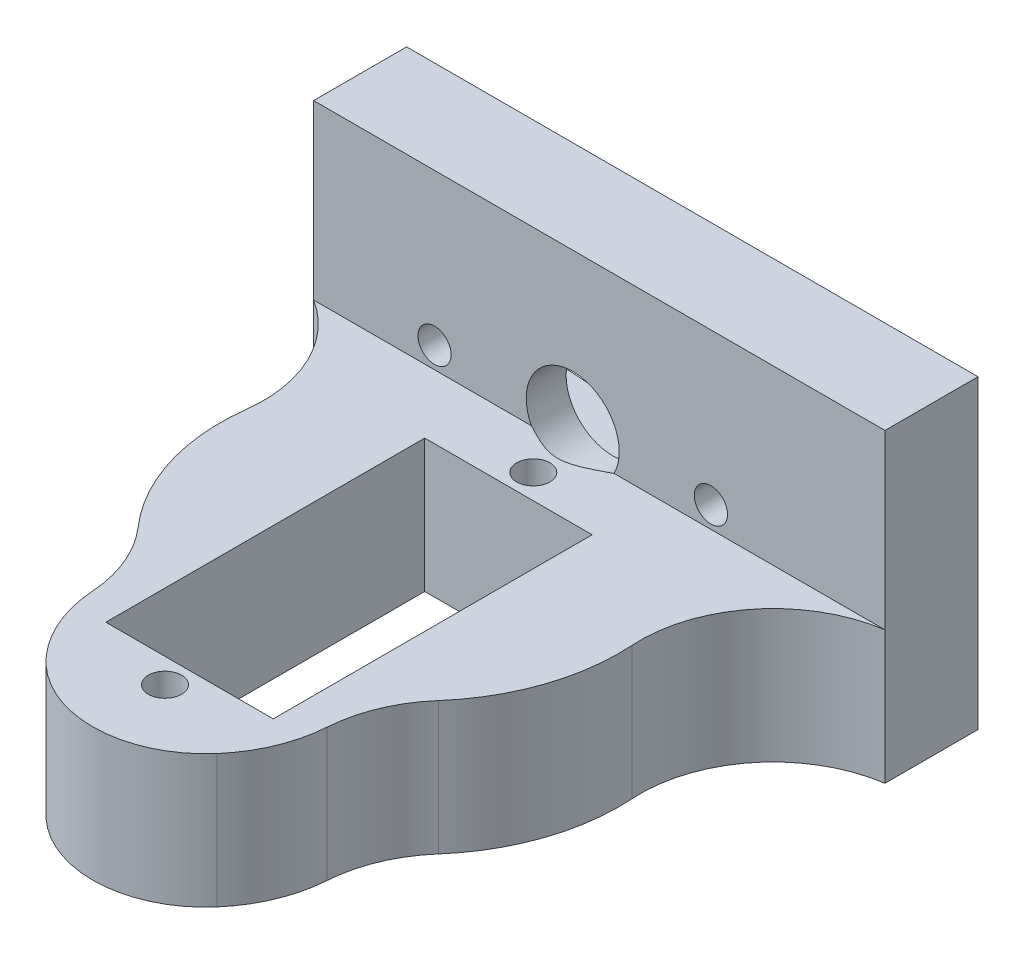
SolidWorks part; units mm, degrees
ref_plane "Front Plane" through (0, 0, 0) normal (0, 0, 1) x (1, 0, 0)
ref_plane "Top Plane" through (0, 0, 0) normal (0, 1, 0) x (1, 0, 0)
ref_plane "Right Plane" through (0, 0, 0) normal (1, 0, 0) x (0, 0, -1)
sketch "Sketch1" plane through (0, 0, 0) normal (0, 0, 1) x (1, 0, 0)
  line L0 (-24.287, 11.4001) -> (-24.287, -11.5999)
  line L1 (-24.287, -11.5999) -> (18.713, -11.5999)
  line L2 (18.713, -11.5999) -> (18.713, 11.4001)
  line L3 (18.713, 11.4001) -> (-24.287, 11.4001)
  line L4 (18.713, 11.5) -> (18.713, -11.5) construction
  dimension "D2" = 23
extrude "Boss-Extrude1" add sketch "Sketch1" along normal blind 7 contours L3 L0 L1 L2
sketch "Sketch13" plane through (0, -11.5999, 0) normal (0, -1, 0) x (1, 0, 0)
  line L0 (-4.787, 0) -> (-4.787, 3.5) construction
  line L1 (-2.0289, 23.8473) -> (-2.1209, 23.6697)
  line L2 (-7.4531, 23.6697) -> (-7.5451, 23.8473)
  line L3 (0.8234, 20.6457) -> (0.9928, 20.7096)
  line L4 (-1.937, 24.0249) -> (-2.0289, 23.8473)
  line L5 (0.9928, 20.7096) -> (0.9928, 34.6188)
  line L6 (0.6928, 34.9188) -> (-10.3072, 34.9188)
  line L7 (-10.6072, 34.6188) -> (-10.6072, 20.7096)
  line L8 (-7.637, 24.0249) -> (-7.637, 24.1188)
  line L9 (-1.937, 24.1188) -> (-1.937, 24.0249)
  line L10 (-7.5451, 23.8473) -> (-7.637, 24.0249)
  line L11 (-10.6072, 20.7096) -> (-10.4024, 20.6323)
  line L12 (0.013, 29.4188) -> (0.013, 33.4188)
  line L13 (-0.487, 33.9188) -> (-9.087, 33.9188)
  line L14 (-9.587, 33.4188) -> (-9.587, 29.4188)
  line L15 (-9.087, 28.9188) -> (-0.487, 28.9188)
  line L16 (-2.5961, 12.7188) -> (0.713, 12.7188)
  line L17 (1.013, 13.0188) -> (1.013, 16.3279)
  line L18 (-10.587, 16.3279) -> (-10.587, 13.0188)
  line L19 (-10.287, 12.7188) -> (-6.9779, 12.7188)
  line L20 (-2.337, 24.0249) -> (-2.337, 24.1188)
  line L21 (-7.237, 24.1188) -> (-7.237, 24.0249)
  line L22 (0.9928, 35.2512) -> (0.9928, 38.9688)
  line L23 (0.1928, 39.7688) -> (-4.4072, 39.7688)
  line L24 (-4.4072, 39.7688) -> (-4.4072, 38.8001)
  line L25 (-5.2072, 38.8001) -> (-5.2072, 39.7688)
  line L26 (-5.2072, 39.7688) -> (-9.8072, 39.7688)
  line L27 (-10.6072, 38.9688) -> (-10.6072, 35.2512)
  line L28 (-10.3072, 35.3188) -> (0.6928, 35.3188)
  line L29 (-10.587, 12.3863) -> (-10.587, 8.6688)
  line L30 (-9.787, 7.8688) -> (-5.187, 7.8688)
  line L31 (-5.187, 7.8688) -> (-5.187, 8.8374)
  line L32 (-4.387, 8.8374) -> (-4.387, 7.8688)
  line L33 (-4.387, 7.8688) -> (0.213, 7.8688)
  line L34 (1.013, 8.6688) -> (1.013, 12.3863)
  line L35 (0.713, 12.3188) -> (-10.287, 12.3188)
  line L36 (2.0332, 31.8996) -> (2.0332, 41.6469)
  line L37 (2.0332, 31.8996) -> (-11.6072, 31.8996)
  line L38 (-11.6072, 31.8996) -> (-11.6072, 41.6469)
  line L39 (2.0332, 41.6469) -> (-11.6072, 41.6469)
  line L40 (-24.287, 0) -> (18.713, 0) construction
  circle A0 centre (-4.787, 18.5188) radius 15.0188
  arc A1 (-7.5451, 23.8473) -> (-2.0289, 23.8473) centre (-4.787, 18.5188) ccw
  arc A2 (0.8234, 20.6457) -> (-2.0289, 23.8473) centre (-4.787, 18.5188) ccw
  arc A3 (0.9928, 34.6188) -> (0.6928, 34.9188) centre (0.6928, 34.6188) ccw
  arc A4 (-10.3072, 34.9188) -> (-10.6072, 34.6188) centre (-10.3072, 34.6188) ccw
  arc A5 (-1.937, 24.1188) -> (-7.637, 24.1188) centre (-4.787, 24.1188) ccw
  arc A6 (-7.5451, 23.8473) -> (-10.4024, 20.6323) centre (-4.787, 18.5188) ccw
  arc A7 (-0.487, 28.9188) -> (0.013, 29.4188) centre (-0.487, 29.4188) ccw
  arc A8 (0.013, 33.4188) -> (-0.487, 33.9188) centre (-0.487, 33.4188) ccw
  arc A9 (-9.087, 33.9188) -> (-9.587, 33.4188) centre (-9.087, 33.4188) ccw
  arc A10 (-9.587, 29.4188) -> (-9.087, 28.9188) centre (-9.087, 29.4188) ccw
  arc A11 (-2.5961, 12.7188) -> (1.013, 16.3279) centre (-4.787, 18.5188) ccw
  arc A12 (0.713, 12.7188) -> (1.013, 13.0188) centre (0.713, 13.0188) ccw
  arc A13 (-10.587, 16.3279) -> (-6.9779, 12.7188) centre (-4.787, 18.5188) ccw
  arc A14 (-10.587, 13.0188) -> (-10.287, 12.7188) centre (-10.287, 13.0188) ccw
  arc A15 (-2.337, 24.0249) -> (-2.1209, 23.6697) centre (-1.937, 24.0249) ccw
  arc A16 (-2.337, 24.1188) -> (-7.237, 24.1188) centre (-4.787, 24.1188) ccw
  arc A17 (-7.4531, 23.6697) -> (-7.237, 24.0249) centre (-7.637, 24.0249) ccw
  arc A18 (0.9928, 35.2512) -> (0.6928, 35.3188) centre (0.6928, 34.6188) ccw
  arc A19 (0.9928, 38.9688) -> (0.1928, 39.7688) centre (0.1928, 38.9688) ccw
  arc A20 (-5.2072, 38.8001) -> (-4.4072, 38.8001) centre (-4.8072, 37.6688) ccw
  arc A21 (-9.8072, 39.7688) -> (-10.6072, 38.9688) centre (-9.8072, 38.9688) ccw
  arc A22 (-10.3072, 35.3188) -> (-10.6072, 35.2512) centre (-10.3072, 34.6188) ccw
  arc A23 (-10.587, 12.3863) -> (-10.287, 12.3188) centre (-10.287, 13.0188) ccw
  arc A24 (-10.587, 8.6688) -> (-9.787, 7.8688) centre (-9.787, 8.6688) ccw
  arc A25 (-4.387, 8.8374) -> (-5.187, 8.8374) centre (-4.787, 9.9688) ccw
  arc A26 (0.213, 7.8688) -> (1.013, 8.6688) centre (0.213, 8.6688) ccw
  arc A27 (0.713, 12.3188) -> (1.013, 12.3863) centre (0.713, 13.0188) ccw
  arc A28 (-2.137, 24.1188) -> (-7.437, 24.1188) centre (-4.787, 24.1188) ccw
  point P6 (-4.7215, 23.4364)
  point P95 (-4.787, 3.5)
  dimension "D4" = 4.787
  dimension "D1" = 15.0188
  dimension "D2" = 1
  dimension "D3" = 0
sketch "Sketch14" plane through (0, -11.5999, 0) normal (0, -1, 0) x (1, 0, 0)
  line L0 (-11.6072, 31.8996) -> (-11.6072, 41.6469) construction
  line L1 (2.0332, 41.6469) -> (-11.6072, 41.6469) construction
  line L2 (2.0332, 31.8996) -> (2.0332, 41.6469) construction
  line L4 (-11.6072, 34.6753) -> (-11.6072, 41.6469)
  line L5 (2.0332, 41.6469) -> (-11.6072, 41.6469)
  line L6 (2.0332, 34.6753) -> (2.0332, 41.6469)
  circle A0 centre (-4.787, 18.5188) radius 15.0188 construction
  arc A1 (-13.6549, 30.6399) -> (4.0809, 30.6399) centre (-4.787, 18.5188) ccw
  arc A2 (2.0332, 34.6753) -> (4.0809, 30.6399) centre (7.0332, 34.6753) ccw
  arc A3 (-11.6072, 34.6753) -> (-13.6549, 30.6399) centre (-16.6072, 34.6753) cw
  dimension "D1" = 5
sketch "Sketch9" plane through (-10, -11.5999, 0) normal (0, 1, 0) x (0, 0, 1)
  line L0 (35.0032, 14.0332) -> (43.6469, 14.0332)
  line L2 (43.6469, 14.0332) -> (43.6469, -3.6072)
  line L3 (30.6747, -3.6072) -> (43.6469, -3.6072)
  line L7 (34.6753, -1.6072) -> (41.6469, -1.6072) construction
  line L8 (41.6469, 12.0332) -> (41.6469, -1.6072) construction
  line L9 (34.6753, 12.0332) -> (41.6469, 12.0332) construction
  line L10 (34.6753, -1.6072) -> (41.6469, -1.6072) construction
  line L11 (41.6469, 12.0332) -> (41.6469, -1.6072) construction
  line L12 (34.6753, 12.0332) -> (41.6469, 12.0332) construction
  line L13 (34.6751, 14.0332) -> (43.6469, 14.0332) construction
  line L14 (34.675, -3.6072) -> (43.6469, -3.6072) construction
  line L15 (43.6469, -3.6072) -> (35.0032, -3.6072)
  arc A0 (30.6803, 14.0255) -> (34.6753, 12.0332) centre (34.6745, 17.0332) ccw construction
  arc A5 (35.0032, 14.0332) -> (28.4144, 16.5108) centre (35.0032, 24.0332) cw
  arc A6 (28.4144, -6.0848) -> (35.0032, -3.6072) centre (35.0032, -13.6072) cw
  circle A7 centre (18.5188, 5.213) radius 15.0188 construction
  arc A9 (28.4144, 16.5108) -> (28.4144, -6.0848) centre (18.5188, 5.213) ccw
  arc A11 (28.4144, 16.5108) -> (28.4144, -6.0848) centre (18.5188, 5.213) ccw
  arc A12 (34.6753, -1.6072) -> (30.6955, -3.5785) centre (34.6738, -6.6072) ccw construction
  arc A13 (34.675, -3.6072) -> (32.2868, -4.79) centre (34.6738, -6.6072) ccw construction
  arc A14 (32.278, 15.2286) -> (34.6751, 14.0332) centre (34.6745, 17.0332) ccw construction
  dimension "D1" = 2
  dimension "D2" = 10
extrude "Boss-Extrude2" add sketch "Sketch9" along normal blind 10
sketch "Sketch2" plane through (0, 0, 0) normal (0, 0, -1) x (-1, 0, 0)
  line L0 (5.0441, -3.5908) -> (8.2109, -3.364) construction
  line L7 (1.3631, -3.364) -> (4.5299, -3.5908) construction
  line L8 (4.5299, 3.5908) -> (1.3631, 3.364) construction
  line L11 (8.2109, 3.364) -> (5.0441, 3.5908) construction
  line L16 (8.2109, -3.364) -> (20.3656, -2.4936) construction
  line L17 (20.3656, 2.4936) -> (8.2109, 3.364) construction
  line L22 (1.3631, 3.364) -> (-10.7916, 2.4936) construction
  line L23 (-10.7916, -2.4936) -> (1.3631, -3.364) construction
  line L24 (1.3274, -3.8627) -> (4.4941, -4.0895)
  line L25 (5.0799, -4.0895) -> (8.2466, -3.8627)
  line L26 (8.2466, -3.8627) -> (20.4013, -2.9923)
  line L27 (20.4013, 2.9923) -> (8.2466, 3.8627)
  line L28 (8.2466, 3.8627) -> (5.0799, 4.0895)
  line L29 (4.4941, 4.0895) -> (1.3274, 3.8627)
  line L30 (1.3274, 3.8627) -> (-10.8273, 2.9923)
  line L31 (-10.8273, -2.9923) -> (1.3274, -3.8627)
  line L32 (0, 0) -> (4.787, 0) construction
  arc A0 (4.4941, -4.0895) -> (5.0799, -4.0895) centre (4.787, 0) ccw
  arc A1 (20.4013, -2.9923) -> (20.4013, 2.9923) centre (20.187, 0) ccw
  arc A2 (4.5299, -3.5908) -> (5.0441, -3.5908) centre (4.787, 0) ccw construction
  arc A3 (5.0441, 3.5908) -> (4.5299, 3.5908) centre (4.787, 0) ccw construction
  arc A4 (5.0799, 4.0895) -> (4.4941, 4.0895) centre (4.787, 0) ccw
  arc A5 (-10.8273, 2.9923) -> (-10.8273, -2.9923) centre (-10.613, 0) ccw
  arc A9 (20.3656, -2.4936) -> (20.3656, 2.4936) centre (20.187, 0) ccw construction
  arc A12 (-10.7916, 2.4936) -> (-10.7916, -2.4936) centre (-10.613, 0) ccw construction
  dimension "D1" = 4.787
extrude "Cut-Extrude1" cut sketch "Sketch2" against normal blind 4
sketch "Sketch3" plane through (0, 0, 4) normal (0, 0, -1) x (-1, 0, 0)
  circle A7 centre (15.187, 0) radius 0.5
  circle A8 centre (-5.613, 0) radius 0.5
  point P19 (-5.613, 0)
  point P20 (15.187, 0)
  point P21 (4.787, 0)
sketch "Sketch6" plane through (0, 0, 4) normal (0, 0, -1) x (-1, 0, 0)
  point P5 (4.787, 0)
hole_wizard "M8x1.0 Tapped Hole1" positions "Sketch6" profile "Sketch7" tap size "M8x1.0" standard "ANSI Metric"
cosmetic thread "Hole Thread3" parameters "D1"=3, "D2"=8
sketch "Sketch7" plane through (-4.787, 0, 4) normal (1, 0, 0) x (0, 1, 0)
  line L0 (0, 0) -> (0, 5.103)
  line L1 (0, 5.103) -> (3.5, 3)
  line L2 (3.5, 3) -> (3.5, 0)
  line L5 (3.5, 0) -> (0, 0)
  line L10 (0, 5.103) -> (-3.5, 3) construction
  line L11 (0, -6.35) -> (0, 107.95) construction
  dimension "Tap Drill Dia." = 7
  dimension "Tap Drill Depth" = 3
  dimension "Drill Angle" = 118
hole_wizard "M3x0.5 Tapped Hole1" positions "Sketch3" profile "Sketch5" tap size "M3x0.5" standard "ANSI Metric" end condition through all
sketch "Sketch5" plane through (-15.187, 0, 4) normal (1, 0, 0) x (0, 1, 0)
  line L0 (0, 0) -> (0, 39.6469)
  line L1 (0, 39.6469) -> (1.25, 39.6469)
  line L2 (1.25, 39.6469) -> (1.25, 0)
  line L5 (1.25, 0) -> (0, 0)
  line L11 (0, -6.35) -> (0, 107.95) construction
  dimension "Thru Tap Drill Dia." = 2.5
  dimension "Thru Tap Drill Depth" = 39.6469
cosmetic thread "Hole Thread1" parameters "D2"=3
cosmetic thread "Hole Thread2" parameters "D2"=3
sketch "Sketch10" plane through (-23, -11.5999, 0) normal (0, 1, 0) x (0, 0, -1)
  line L4 (-12.3188, -23.9928) -> (-35.3188, -23.9928) construction
  line L5 (-12.3188, -23.9928) -> (-12.3188, -12.3928) construction
  line L6 (-35.3188, -12.3928) -> (-12.3188, -12.3928) construction
  line L7 (-35.3188, -12.3928) -> (-35.3188, -23.9928) construction
  line L8 (-35.8188, -11.8928) -> (-11.8188, -11.8928)
  line L9 (-11.8188, -24.4928) -> (-11.8188, -11.8928)
  line L10 (-11.8188, -24.4928) -> (-35.8188, -24.4928)
  line L11 (-35.8188, -11.8928) -> (-35.8188, -24.4928)
  line L12 (-34.6188, -12.3928) -> (-20.7096, -12.3928) construction
  line L13 (-20.7096, -23.9928) -> (-34.6188, -23.9928) construction
  line L14 (-35.3188, -12.6928) -> (-35.3188, -23.6928) construction
  line L15 (-12.3188, -23.713) -> (-12.3188, -12.713) construction
  dimension "D2" = 23
  dimension "D1" = 0.5
extrude "Cut-Extrude2" cut sketch "Sketch10" along normal through all contours L8 L9 L10 L11
sketch "Sketch11" plane through (-13, -1.5999, 0) normal (0, 1, 0) x (0, 0, -1)
  point P5 (-37.6688, -8.1928)
  point P8 (-9.9688, -8.213)
hole_wizard "M3x0.5 Tapped Hole2" positions "Sketch11" profile "Sketch12" tap size "M3x0.5" standard "ANSI Metric"
sketch "Sketch12" plane through (-4.8072, -1.5999, 37.6688) normal (1, 0, 0) x (0, 0, 1)
  line L0 (0, 0) -> (0, 8.5)
  line L1 (0, 8.5) -> (1.25, 7.7489)
  line L2 (1.25, 7.7489) -> (1.25, 0)
  line L5 (1.25, 0) -> (0, 0)
  line L10 (0, 8.5) -> (-1.25, 7.7489) construction
  line L11 (0, -6.35) -> (0, 107.95) construction
  dimension "Tap Drill Dia." = 2.5
  dimension "Tap Drill Depth" = 8.5
  dimension "Drill Angle" = 118
cosmetic thread "Hole Thread7" parameters "D1"=6, "D2"=3.5
cosmetic thread "Hole Thread8" parameters "D1"=6, "D2"=3.5
fillet "Fillet2" radius 10 1 edges at (-14.4245, -6.5999, 7)
fillet "Fillet3" radius 10 2 edges at (-13.6072, -6.5999, 43.6469) (4.0332, -6.5999, 43.6469)
fillet "Fillet4" radius 8.5 1 edges at (-4.787, -6.5999, 43.5824)
